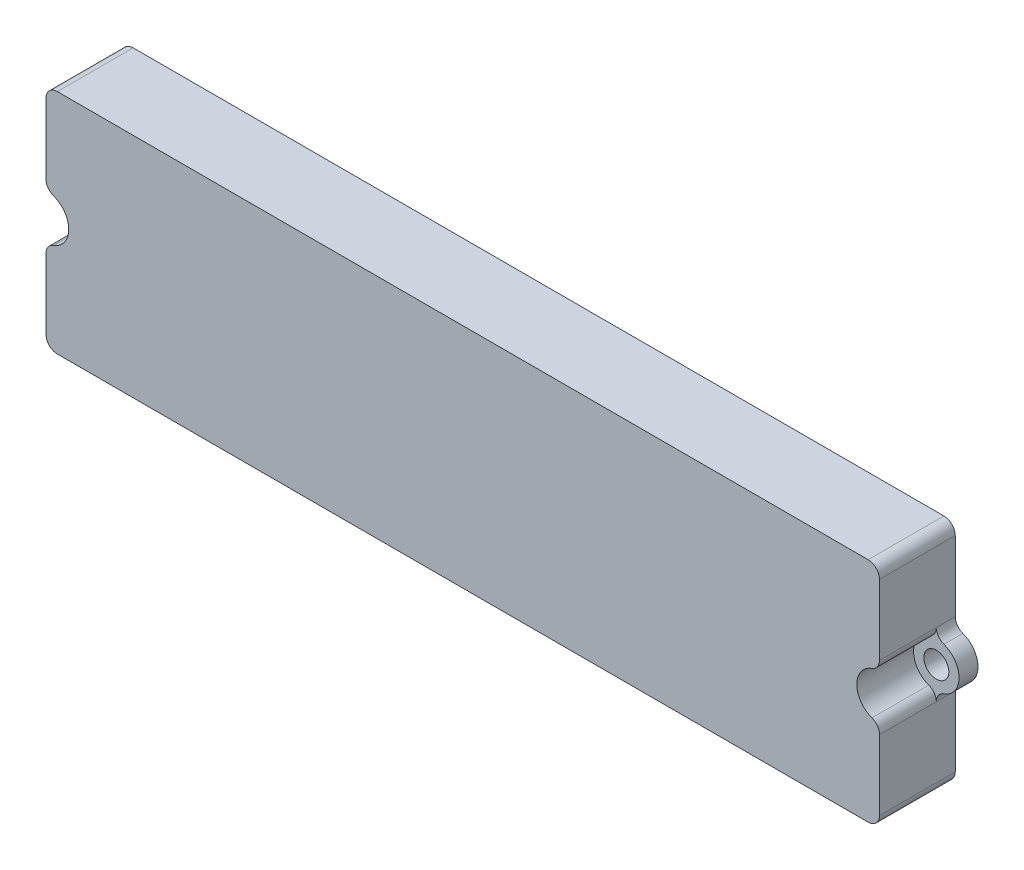
SolidWorks part; units mm, degrees
ref_plane "Front Plane" through (0, 0, 0) normal (0, 0, 1) x (1, 0, 0)
ref_plane "Top Plane" through (0, 0, 0) normal (0, 1, 0) x (1, 0, 0)
ref_plane "Right Plane" through (0, 0, 0) normal (1, 0, 0) x (0, 0, -1)
sketch "Sketch1" plane through (0, 0, 0) normal (0, 0, 1) x (1, 0, 0)
  line L1 (-110, -30) -> (110, -30)
  line L2 (-110, -30) -> (-110, 30)
  line L3 (-110, 30) -> (110, 30)
  line L4 (110, -30) -> (110, 30)
  line L5 (-110, -30) -> (110, 30) construction
  line L6 (-110, 30) -> (110, -30) construction
  point P0 (0, 0)
  dimension "D1" = 60
  dimension "D2" = 220
extrude "Boss-Extrude1" add sketch "Sketch1" along normal blind 20
fillet "Fillet1" radius 3 4 edges at (-110, -30, 10) (110, -30, 10) (110, 30, 10) (-110, 30, 10)
sketch "Sketch2" plane through (0, 0, 20) normal (0, 0, 1) x (1, 0, 0)
  line L0 (-110, 27) -> (-110, -27) construction
  line L1 (110, -27) -> (110, 27) construction
  circle A0 centre (-110, 0) radius 6
  circle A1 centre (110, 0) radius 6
  dimension "D1" = 12
  dimension "D2" = 12
extrude "Boss-Extrude2" add sketch "Sketch2" against normal up to surface (20 mm away) up to face at (0, 0, 0)
sketch "Sketch3" plane through (0, 0, 20) normal (0, 0, 1) x (1, 0, 0)
  circle A0 centre (-110, 0) radius 3.3
  circle A1 centre (110, 0) radius 3.3
  dimension "D1" = 6.6
  dimension "D2" = 6.6
extrude "Cut-Extrude1" cut sketch "Sketch3" against normal blind 20
sketch "Sketch4" plane through (0, 0, 20) normal (0, 0, 1) x (1, 0, 0)
  circle A0 centre (-110, 0) radius 6
  circle A1 centre (110, 0) radius 6
  dimension "D1" = 12
  dimension "D2" = 12
extrude "Cut-Extrude2" cut sketch "Sketch4" against normal blind 15
fillet "Fillet2" radius 3 2 edges at (-110, -6, 2.5) (-110, 6, 2.5)
fillet "Fillet3" radius 3 1 edges at (-110, 6, 12.5)
fillet "Fillet4" radius 3 1 edges at (-110, -6, 12.5)
fillet "Fillet6" radius 3 2 edges at (110, -6, 2.5) (110, 6, 2.5)
fillet "Fillet7" radius 3 2 edges at (110, -6, 12.5) (110, 6, 12.5)
